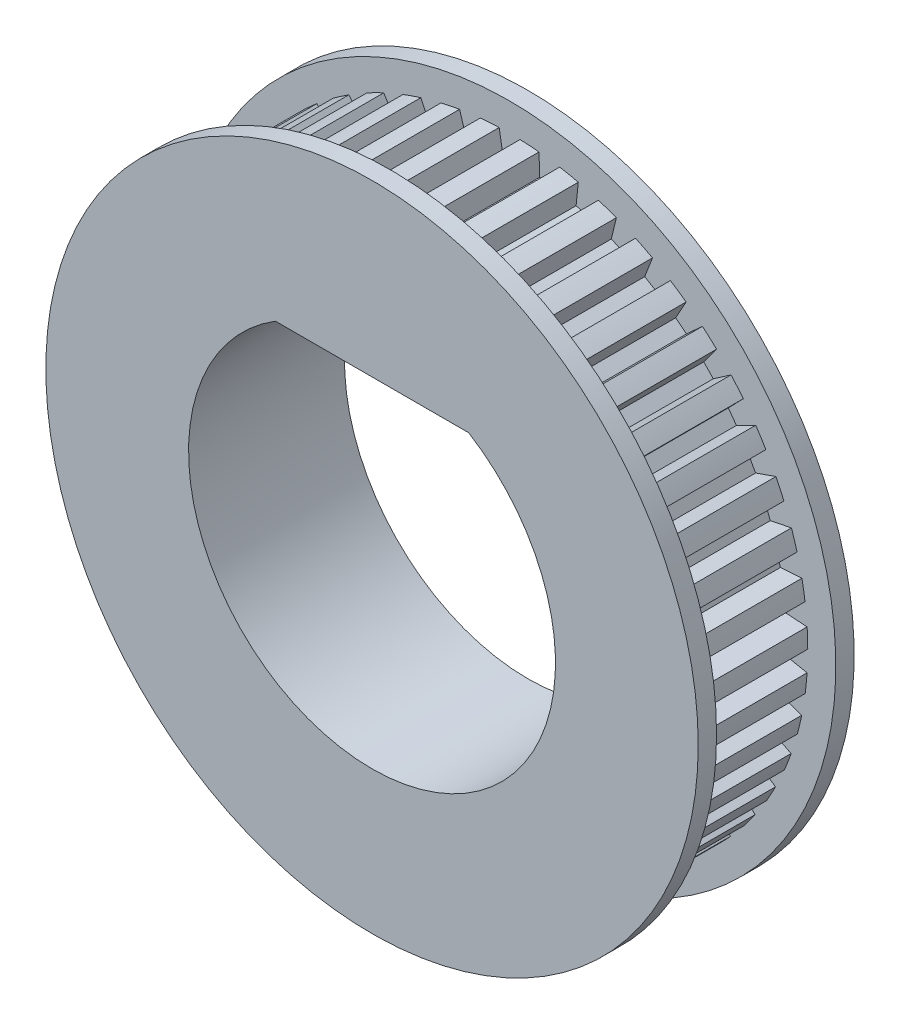
SolidWorks part; units mm, degrees
ref_plane "Front Plane" through (0, 0, 0) normal (0, 0, 1) x (1, 0, 0)
ref_plane "Top Plane" through (0, 0, 0) normal (0, 1, 0) x (1, 0, 0)
ref_plane "Right Plane" through (0, 0, 0) normal (1, 0, 0) x (0, 0, -1)
sketch "Sketch3" plane through (0, 0, 0) normal (0, 0, 1) x (1, 0, 0)
  circle A0 centre (0, 0) radius 16.25
  dimension "D1" = 32.5
extrude "Boss-Extrude2" add sketch "Sketch3" along normal mid plane 6.5
sketch "Sketch1" plane through (0, 0, 0) normal (0, 0, 1) x (1, 0, 0)
  line L0 (-0.375, 15.08) -> (0.375, 15.08)
  line L2 (-0.375, 15.08) -> (-0.6543, 16.7561)
  line L3 (-0.6543, 16.7561) -> (0.6543, 16.7561)
  line L4 (0.6543, 16.7561) -> (0.375, 15.08)
  line L5 (-0.5, 15.83) -> (0.5, 15.83) construction
  point P9 (0, 16.7561)
  point P10 (0, 15.08)
  dimension "D1" = 0.75
  dimension "D2" = 0.75
  dimension "D3" = 1
  dimension "D4" = 15.08
extrude "Cut-Extrude2" cut sketch "Sketch1" against normal through all both and the other way through all
pattern_circular "CirPattern3" count 47 over 360 about axis through (0, 0, 3.25) along (0, 0, 1) of "Cut-Extrude2"
sketch "Sketch5" plane through (0, 0, -3.25) normal (0, 0, -1) x (-1, 0, 0)
  circle A0 centre (0, 0) radius 17.78
  dimension "D1" = 35.56
extrude "Boss-Extrude3" add sketch "Sketch5" along normal blind 1
sketch "Sketch6" plane through (0, 0, 3.25) normal (0, 0, 1) x (1, 0, 0)
  circle A0 centre (0, 0) radius 17.78
  dimension "D1" = 35.56
extrude "Boss-Extrude4" add sketch "Sketch6" along normal blind 1
sketch "Sketch7" plane through (0, 0, 4.25) normal (0, 0, 1) x (1, 0, 0)
  line L0 (-5.2678, 8.5) -> (5.2678, 8.5)
  circle A0 centre (0, 0) radius 10
  point P2 (-5.2678, 8.5)
  point P5 (0, 8.5)
  dimension "D1" = 20
  dimension "D2" = 8.5
extrude "Cut-Extrude3" cut sketch "Sketch7" against normal through all both and the other way through all contours L0 A0 region at (0, -0.3212, 4.25)
